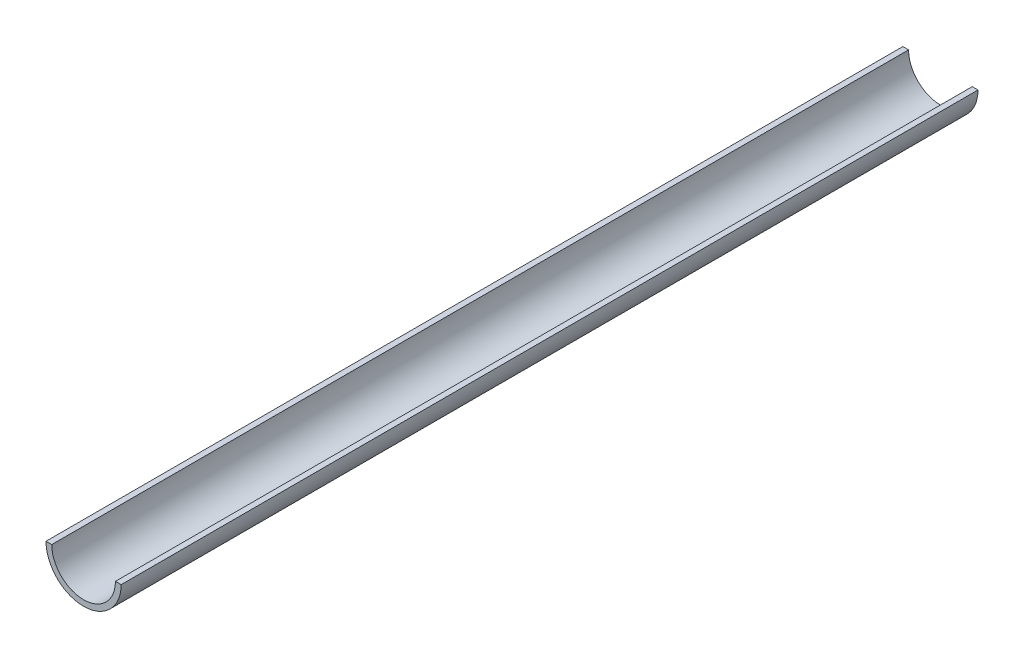
SolidWorks part; units mm, degrees
ref_plane "Front Plane" through (0, 0, 0) normal (0, 0, 1) x (1, 0, 0)
ref_plane "Top Plane" through (0, 0, 0) normal (0, 1, 0) x (1, 0, 0)
ref_plane "Right Plane" through (0, 0, 0) normal (1, 0, 0) x (0, 0, -1)
sketch "Sketch1" plane through (0, 0, 0) normal (0, 0, 1) x (1, 0, 0)
  line L0 (-24.13, 0) -> (-20.445, 0)
  line L1 (20.445, 0) -> (24.13, 0)
  arc A0 (-24.13, 0) -> (24.13, 0) centre (0, 0) ccw
  arc A1 (-20.445, 0) -> (20.445, 0) centre (0, 0) ccw
  dimension "D1" = 20.445
  dimension "D2" = 24.13
extrude "Boss-Extrude1" add sketch "Sketch1" along normal mid plane 550.14
ref_axis "Axis1" through (0, 0, 275.07) along (0, 0, -1)
